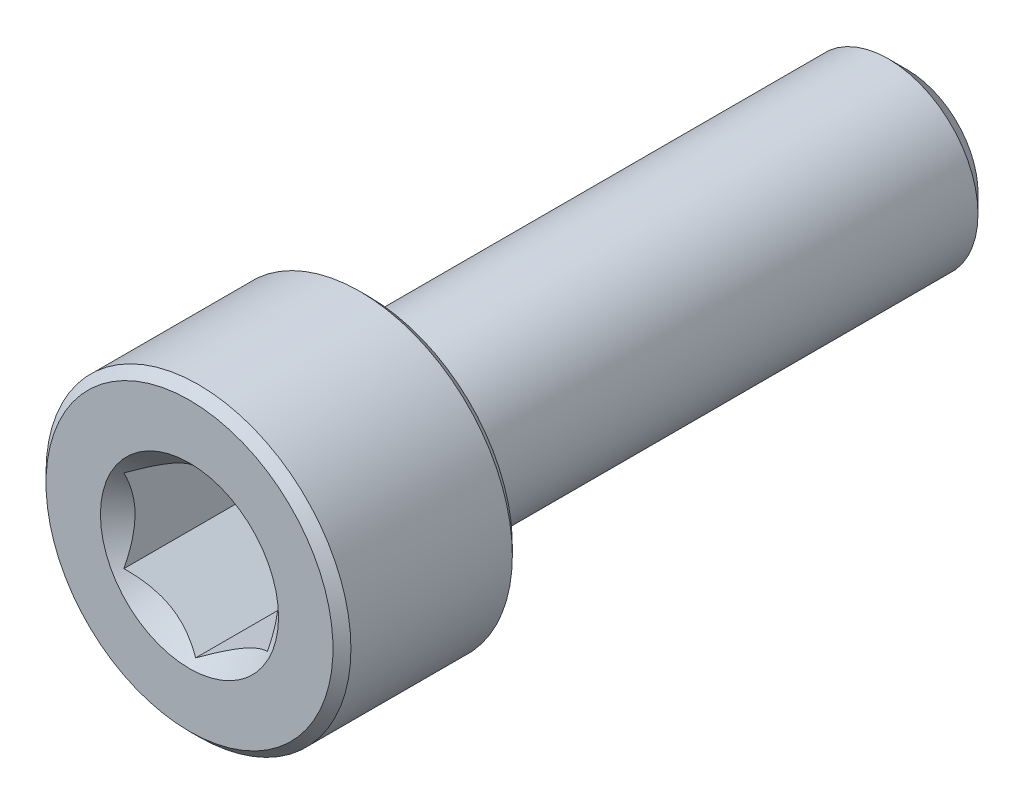
SolidWorks part; units mm, degrees
ref_plane "Front Plane" through (0, 0, 0) normal (0, 0, 1) x (1, 0, 0)
ref_plane "Top Plane" through (0, 0, 0) normal (0, 1, 0) x (1, 0, 0)
ref_plane "Right Plane" through (0, 0, 0) normal (1, 0, 0) x (0, 0, -1)
sketch "Sketch1" plane through (0, 0, 0) normal (1, 0, 0) x (0, 0, -1)
  line L0 (-10, 0) -> (10, 0) construction
  line L1 (10, 0) -> (10, 1.9804) construction
  line L2 (10, 1.9804) -> (9.4804, 2.5) construction
  line L3 (9.4804, 2.5) -> (9.4, 2.5) construction
  line L4 (9.4, 2.5) -> (-5, 2.5) construction
  line L5 (-5, 2.5) -> (-5, 4.25) construction
  line L6 (-5, 4.25) -> (-10, 4.25) construction
  line L7 (-10, 4.25) -> (-10, 0) construction
  line L8 (10, 1.9804) -> (10, 2.5) construction
  line L9 (9.95, 2.5866) -> (10.35, 1.8938) construction
  line L10 (10.35, 1.8938) -> (10.75, 2.5866) construction
  line L11 (10.75, 2.5866) -> (9.95, 2.5866) construction
  line L12 (10.35, 2.5866) -> (10.35, 2.5) construction
  line L13 (10.35, 1.8938) -> (10.35, 1.9804) construction
  line L14 (10.3, 1.9804) -> (10.4, 1.9804) construction
  line L15 (10, 2.5) -> (10.7, 2.5) construction
  line L16 (9.975, 2.5433) -> (10.725, 2.5433) construction
  line L17 (10, 0) -> (10, -2.5) construction
  line L18 (-5.25, 4.25) -> (-5, 4) construction
  line L19 (-9.75, 4.25) -> (-10, 4) construction
  line L20 (-5, 2.5) -> (-5, 0) construction
  line L21 (-5, 1.25) -> (0, 1.25) construction
  line L22 (0, 1.25) -> (5, 1.25) construction
  line L23 (5, 1.25) -> (10, 1.25) construction
  line L24 (0, 1.25) -> (0, 2.5) construction
  line L25 (0, 2.5) -> (0, 4.25) construction
  line L26 (5, 1.25) -> (5, 4.25) construction
  point P0 (-10, 2)
  point P3 (8, 2.5)
  point P4 (0, 0)
  point P18 (5, 2.5)
  point P22 (10.35, 1.9804)
  point P24 (9.4, 2.5)
  point P25 (10.35, 2.5)
  point P28 (10.35, 2.5433)
  point P29 (8, -2.5)
  point P30 (0, 2.5)
  point P31 (-7.5, 4.25)
  point P37 (-5.875, 4.25)
  point P38 (-9.625, 4.25)
  point P45 (0, 1.25)
  point P46 (5, 1.25)
  dimension "D2" = 0.1
  dimension "D7" = 0.25
  dimension "D8" = 0.25
  dimension "D9" = 0.25
  dimension "D10" = 0.125
  dimension "D11" = 0.625
  dimension "Drive Size" = 4
  dimension "Head Diameter" = 8.5
  dimension "Head Height" = 5
  dimension "Thread Pitch" = 0.8
  dimension "Thread Dia" = 5
  dimension "Length" = 15
  dimension "D12" = 0.6
  dimension "D4" = 2
  dimension "D3" = 45
sketch "Sketch2" plane through (0, 0, 0) normal (1, 0, 0) x (0, 0, -1)
  line L0 (-10, 0) -> (-10, 4)
  line L1 (-9.75, 4.25) -> (-5.25, 4.25)
  line L2 (-5, 4) -> (-5, 2.75)
  line L4 (9.4804, 2.5) -> (10, 1.9804)
  line L5 (10, 1.9804) -> (10, 0)
  line L6 (-5, 4.25) -> (-10, 4.25) construction
  line L7 (10, 0) -> (-10, 0)
  line L8 (-9.75, 4.25) -> (-10, 4) construction
  line L10 (-9.75, 4.25) -> (-10, 4)
  line L14 (-5.25, 4.25) -> (-5, 4) construction
  line L16 (-5.25, 4.25) -> (-5, 4)
  line L17 (-5, 2.5) -> (-5, 4.25) construction
  line L19 (-4.75, 2.5) -> (9.4804, 2.5)
  line L20 (9.4, 2.5) -> (-5, 2.5) construction
  arc A1 (-5, 2.75) -> (-4.75, 2.5) centre (-4.75, 2.75) ccw
  dimension "D3" = 0.25
revolve "Revolve1" add sketch "Sketch2" angle 360 about L7
sketch "Sketch3" plane through (0, 0, 10) normal (0, 0, 1) x (1, 0, 0)
  line L1 (2, -1.1547) -> (2, 1.1547)
  line L2 (2, 1.1547) -> (0, 2.3094)
  line L3 (0, 2.3094) -> (-2, 1.1547)
  line L4 (-2, 1.1547) -> (-2, -1.1547)
  line L5 (-2, -1.1547) -> (0, -2.3094)
  line L6 (0, -2.3094) -> (2, -1.1547)
  circle A0 centre (0, 0) radius 2 construction
  circle A1 centre (0, 0) radius 4.25 construction
  circle A2 centre (0, 0) radius 4.25 construction
  circle A3 centre (0, 0) radius 2.3094 construction
  point P13 (0, 0)
  dimension "D1" = 4.6188
extrude "Cut-Extrude1" cut sketch "Sketch3" against normal offset from surface (4 mm away) 1 up to face at (0, 4, 5)
sketch "Sketch4" plane through (0, 0, 10) normal (0, 0, 1) x (1, 0, 0)
  circle A0 centre (0, 0) radius 2.4826
  dimension "D1" = 4.9652
extrude "Cut-Extrude2" cut sketch "Sketch4" against normal up to vertex (2.5 mm away) draft 45 up to point (0, 4.25, 7.5)
sketch "Sketch11" plane through (0, 0, 0) normal (1, 0, 0) x (0, 0, -1)
  line L0 (-10, 0) -> (10, 0) construction
  line L1 (-10, 0) -> (10, 0) construction
  line L2 (-2.1875, 0) -> (-2.1875, 2.5) construction
  line L3 (9.4, 2.5) -> (-5, 2.5) construction
  line L4 (7.1875, 0) -> (7.1875, 2.5) construction
  line L6 (10, 1.9804) -> (10, 2.5) construction
  point P2 (-2.1875, 0)
  point P3 (7.1875, 0)
  dimension "D1" = 2.8125
  dimension "D2" = 2.8125
sketch "Sketch6" [suppressed] plane through (0, 0, -10) normal (0, 0, -1) x (-1, 0, 0)
  circle A0 centre (0, 0) radius 2.5
curve "Helix/Spiral1" [suppressed] pitch 0.8 height 15.8 turns 19.75
sketch "Sketch10" [suppressed] plane through (0, 0, 0) normal (1, 0, 0) x (0, 0, -1)
  line L0 (-4.75, -4.25) -> (-4.75, 4.25)
  line L5 (-10, 0) -> (10, 0) construction
  line L6 (-4.75, 2.5) -> (-4.75, -2.5) construction
  point P3 (-4.75, 0)
split "Split1" [suppressed] bodies to split 106
sketch "Sketch7" [suppressed] plane through (0, 0, 0) normal (1, 0, 0) x (0, 0, -1)
  line L0 (9.975, 2.5433) -> (10.725, 2.5433)
  line L1 (10.725, 2.5433) -> (10.4, 1.9804)
  line L2 (10.4, 1.9804) -> (10.3, 1.9804)
  line L3 (10.3, 1.9804) -> (9.975, 2.5433)
sweep "Cut-Sweep1" [suppressed] cut profiles "Sketch7" path "Helix/Spiral1"
sketch "Sketch8" [suppressed] plane through (0, 0, 0) normal (1, 0, 0) x (0, 0, -1)
  line L0 (-5, 0) -> (-5, 2.5)
  line L1 (-4.75, -2.5) -> (-4.75, 2.5) construction
  line L2 (-5, 2.5) -> (-4.75, 2.5)
  line L4 (-4.75, 2.5) -> (-3.3066, 0)
  line L5 (-3.3066, 0) -> (-5, 0)
  line L6 (9.4, 2.5) -> (-5, 2.5) construction
  line L7 (-10, 0) -> (10, 0) construction
  dimension "D1" = 60
revolve "Revolve2" [suppressed] add sketch "Sketch8" angle 360 about L5
equation "\"D2@Sketch1\" = \"Thread Pitch@Sketch1\" / 8"
equation "\"D4@Helix/Spiral1\" = \"Thread Pitch@Sketch1\""
equation "\"D7@Sketch1\" = \"Head Height@Sketch1\" * .05"
equation "\"D8@Sketch1\"=\"D7@Sketch1\""
equation "\"D9@Sketch1\"=\"D7@Sketch1\""
equation "\"D10@Sketch1\"=\"D7@Sketch1\"/2"
equation "\"D11@Sketch1\"=\"D10@Sketch1\"*5"
equation "\"D4@Sketch1\"=\"Thread Pitch@Sketch1\"*2.5"
equation "\"D12@Sketch1\"=\"Thread Pitch@Sketch1\"*.75"
equation "\"D3@Helix/Spiral1\"=\"Length@Sketch1\"+\"Thread Pitch@Sketch1\""
equation "\"D3@Sketch2\"=\"Thread Dia@Sketch1\"*0.05"
equation "\"D1@Sketch11\"=\"Length@Sketch1\"*0.1875"
equation "\"D2@Sketch11\"=\"D1@Sketch11\""
equation "\"D1@Sketch4\"=\"D1@Sketch3\"*1.075"
